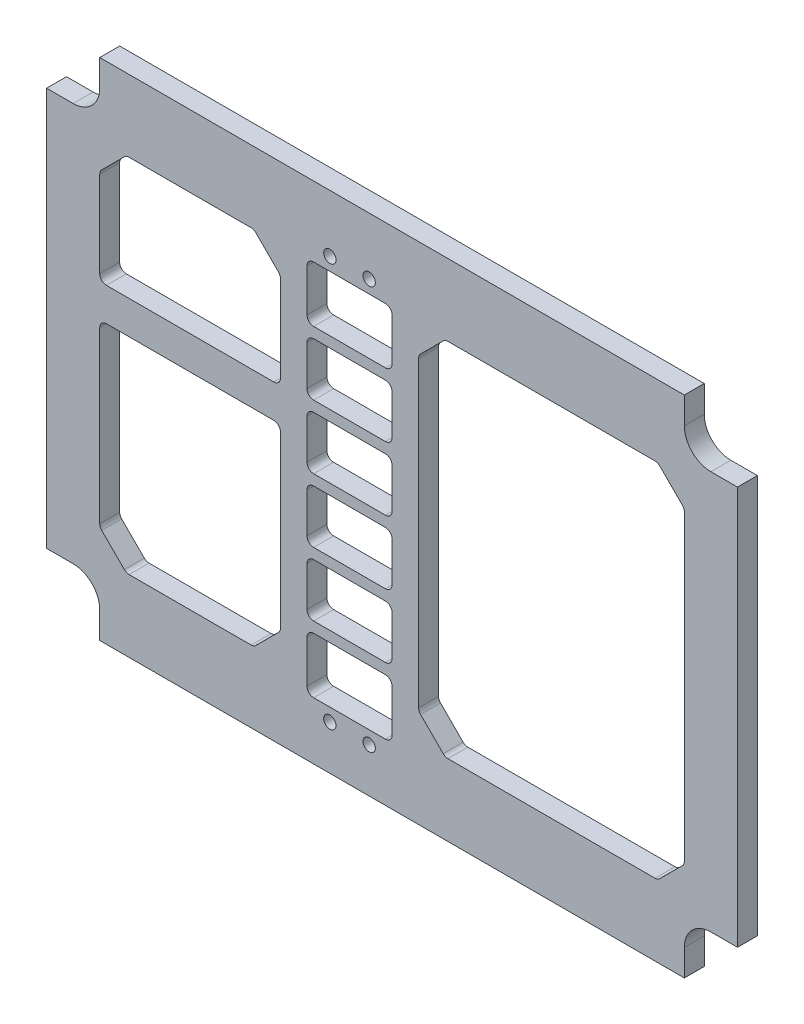
SolidWorks part; units mm, degrees
ref_plane "Front Plane" through (0, 0, 0) normal (0, 0, 1) x (1, 0, 0)
ref_plane "Top Plane" through (0, 0, 0) normal (0, 1, 0) x (1, 0, 0)
ref_plane "Right Plane" through (0, 0, 0) normal (1, 0, 0) x (0, 0, -1)
sketch "Sketch1" plane through (0, 0, 0) normal (0, 0, 1) x (1, 0, 0)
  line L0 (0, -12.7) -> (-6.35, -12.7) construction
  line L1 (-12.7, -6.35) -> (-12.7, 0) construction
  line L2 (-12.7, 0) -> (-152.4, 0) construction
  line L3 (-152.4, 0) -> (-152.4, -6.35) construction
  line L4 (-158.75, -12.7) -> (-165.1, -12.7) construction
  line L5 (-165.1, -12.7) -> (-165.1, -107.95) construction
  line L6 (-165.1, -107.95) -> (-158.75, -107.95) construction
  line L7 (-152.4, -114.3) -> (-152.4, -120.65) construction
  line L8 (-152.4, -120.65) -> (-12.7, -120.65) construction
  line L9 (-12.7, -120.65) -> (-12.7, -114.3) construction
  line L10 (-6.35, -107.95) -> (0, -107.95) construction
  line L11 (0, -107.95) -> (0, -12.7) construction
  line L12 (-102.87, -112.014) -> (-82.55, -112.014) construction
  line L13 (-82.55, -112.014) -> (-82.55, -11.684) construction
  line L14 (-82.55, -11.684) -> (-102.87, -11.684) construction
  line L15 (-102.87, -11.684) -> (-102.87, -112.014) construction
  line L16 (-19.05, -17.145) -> (-69.85, -17.145) construction
  line L17 (-69.85, -17.145) -> (-76.2, -23.495) construction
  line L18 (-76.2, -23.495) -> (-76.2, -97.155) construction
  line L19 (-76.2, -97.155) -> (-69.85, -103.505) construction
  line L20 (-69.85, -103.505) -> (-19.05, -103.505) construction
  line L21 (-19.05, -103.505) -> (-12.7, -97.155) construction
  line L22 (-12.7, -97.155) -> (-12.7, -23.495) construction
  line L23 (-12.7, -23.495) -> (-19.05, -17.145) construction
  line L24 (-152.4, -23.495) -> (-152.4, -46.355) construction
  line L25 (-152.4, -46.355) -> (-109.22, -46.355) construction
  line L26 (-109.22, -46.355) -> (-109.22, -23.495) construction
  line L27 (-109.22, -23.495) -> (-115.57, -17.145) construction
  line L28 (-115.57, -17.145) -> (-146.05, -17.145) construction
  line L29 (-146.05, -17.145) -> (-152.4, -23.495) construction
  line L30 (-109.22, -97.155) -> (-109.22, -54.2925) construction
  line L31 (-109.22, -54.2925) -> (-152.4, -54.2925) construction
  line L32 (-152.4, -54.2925) -> (-152.4, -97.155) construction
  line L33 (-152.4, -97.155) -> (-146.05, -103.505) construction
  line L34 (-146.05, -103.505) -> (-115.57, -103.505) construction
  line L35 (-115.57, -103.505) -> (-109.22, -97.155) construction
  line L36 (0, -12.7) -> (-6.35, -12.7)
  line L37 (-12.7, -6.35) -> (-12.7, 0)
  line L38 (-12.7, 0) -> (-152.4, 0)
  line L39 (-152.4, 0) -> (-152.4, -6.35)
  line L40 (-158.75, -12.7) -> (-165.1, -12.7)
  line L41 (-165.1, -12.7) -> (-165.1, -107.95)
  line L42 (-165.1, -107.95) -> (-158.75, -107.95)
  line L43 (-152.4, -114.3) -> (-152.4, -120.65)
  line L44 (-152.4, -120.65) -> (-12.7, -120.65)
  line L45 (-12.7, -120.65) -> (-12.7, -114.3)
  line L46 (-6.35, -107.95) -> (0, -107.95)
  line L47 (0, -107.95) -> (0, -12.7)
  line L48 (-102.87, -112.014) -> (-82.55, -112.014)
  line L49 (-82.55, -112.014) -> (-82.55, -11.684)
  line L50 (-82.55, -11.684) -> (-102.87, -11.684)
  line L51 (-102.87, -11.684) -> (-102.87, -112.014)
  line L52 (-19.05, -17.145) -> (-69.85, -17.145)
  line L53 (-69.85, -17.145) -> (-76.2, -23.495)
  line L54 (-76.2, -23.495) -> (-76.2, -97.155)
  line L55 (-76.2, -97.155) -> (-69.85, -103.505)
  line L56 (-69.85, -103.505) -> (-19.05, -103.505)
  line L57 (-19.05, -103.505) -> (-12.7, -97.155)
  line L58 (-12.7, -97.155) -> (-12.7, -23.495)
  line L59 (-12.7, -23.495) -> (-19.05, -17.145)
  line L60 (-152.4, -23.495) -> (-152.4, -46.355)
  line L61 (-152.4, -46.355) -> (-109.22, -46.355)
  line L62 (-109.22, -46.355) -> (-109.22, -23.495)
  line L63 (-109.22, -23.495) -> (-115.57, -17.145)
  line L64 (-115.57, -17.145) -> (-146.05, -17.145)
  line L65 (-146.05, -17.145) -> (-152.4, -23.495)
  line L66 (-109.22, -97.155) -> (-109.22, -54.2925)
  line L67 (-109.22, -54.2925) -> (-152.4, -54.2925)
  line L68 (-152.4, -54.2925) -> (-152.4, -97.155)
  line L69 (-152.4, -97.155) -> (-146.05, -103.505)
  line L70 (-146.05, -103.505) -> (-115.57, -103.505)
  line L71 (-115.57, -103.505) -> (-109.22, -97.155)
  arc A0 (-12.7, -6.35) -> (-6.35, -12.7) centre (-6.35, -6.35) ccw construction
  arc A1 (-158.75, -12.7) -> (-152.4, -6.35) centre (-158.75, -6.35) ccw construction
  arc A2 (-152.4, -114.3) -> (-158.75, -107.95) centre (-158.75, -114.3) ccw construction
  arc A3 (-6.35, -107.95) -> (-12.7, -114.3) centre (-6.35, -114.3) ccw construction
  arc A4 (-12.7, -6.35) -> (-6.35, -12.7) centre (-6.35, -6.35) ccw
  arc A5 (-158.75, -12.7) -> (-152.4, -6.35) centre (-158.75, -6.35) ccw
  arc A6 (-152.4, -114.3) -> (-158.75, -107.95) centre (-158.75, -114.3) ccw
  arc A7 (-6.35, -107.95) -> (-12.7, -114.3) centre (-6.35, -114.3) ccw
extrude "Boss-Extrude1" add sketch "Sketch1" along normal blind 4.7625
sketch "Sketch2" plane through (0, 0, 0) normal (0, 0, -1) x (-1, 0, 0)
  line L9 (105.87, -115.014) -> (105.87, -8.684)
  line L10 (79.55, -115.014) -> (105.87, -115.014)
  line L11 (79.55, -8.684) -> (79.55, -115.014)
  line L12 (105.87, -8.684) -> (79.55, -8.684)
  line L13 (105.87, -115.014) -> (105.87, -8.684)
  line L14 (79.55, -115.014) -> (105.87, -115.014)
  line L15 (79.55, -8.684) -> (79.55, -115.014)
  line L16 (105.87, -8.684) -> (79.55, -8.684)
  dimension "D1" = 3
extrude "Cut-Extrude1" cut sketch "Sketch2" against normal through all
fillet "Fillet1" radius 1.5875 24 edges at (-109.22, -54.2925, 2.3813) (-152.4, -54.2925, 2.3813) (-146.05, -103.505, 2.3813) (-115.57, -103.505, 2.3813) (-109.22, -97.155, 2.3813) (-152.4, -46.355, 2.3813) (-109.22, -46.355, 2.3813) (-109.22, -23.495, 2.3813) (-115.57, -17.145, 2.3813) (-146.05, -17.145, 2.3813) (-152.4, -23.495, 2.3813) (-69.85, -17.145, 2.3813) (-76.2, -23.495, 2.3813) (-76.2, -97.155, 2.3813) (-69.85, -103.505, 2.3813) (-19.05, -103.505, 2.3813) (-12.7, -97.155, 2.3813) (-12.7, -23.495, 2.3813) (-19.05, -17.145, 2.3813) (-79.55, -115.014, 2.3813) (-79.55, -8.684, 2.3813) (-105.87, -8.684, 2.3813) (-105.87, -115.014, 2.3813) (-152.4, -97.155, 2.3813)
sketch "Sketch4" plane through (0, 0, 4.7625) normal (0, 0, 1) x (1, 0, 0)
  line L0 (-79.55, -10.2715) -> (-79.55, -113.4265) construction
  line L1 (-81.1375, -115.014) -> (-104.2825, -115.014) construction
  line L2 (-105.87, -113.4265) -> (-105.87, -10.2715) construction
  line L3 (-104.2825, -8.684) -> (-81.1375, -8.684) construction
  line L4 (-79.55, -10.2715) -> (-79.55, -113.4265)
  line L5 (-81.1375, -115.014) -> (-104.2825, -115.014)
  line L6 (-105.87, -113.4265) -> (-105.87, -10.2715)
  line L7 (-104.2825, -8.684) -> (-81.1375, -8.684)
  line L8 (-82.55, -18.3515) -> (-82.55, -28.5115) construction
  line L9 (-84.1375, -30.099) -> (-101.2825, -30.099) construction
  line L10 (-102.87, -28.5115) -> (-102.87, -18.3515) construction
  line L12 (-82.55, -34.2265) -> (-82.55, -43.7515) construction
  line L13 (-84.1375, -45.339) -> (-101.2825, -45.339) construction
  line L14 (-102.87, -43.7515) -> (-102.87, -34.2265) construction
  line L15 (-101.2825, -32.639) -> (-84.1375, -32.639) construction
  line L16 (-82.55, -49.4665) -> (-82.55, -58.9915) construction
  line L17 (-84.1375, -60.579) -> (-101.2825, -60.579) construction
  line L18 (-102.87, -58.9915) -> (-102.87, -49.4665) construction
  line L19 (-101.2825, -47.879) -> (-84.1375, -47.879) construction
  line L20 (-82.55, -64.7065) -> (-82.55, -74.2315) construction
  line L21 (-84.1375, -75.819) -> (-101.2825, -75.819) construction
  line L22 (-102.87, -74.2315) -> (-102.87, -64.7065) construction
  line L23 (-101.2825, -63.119) -> (-84.1375, -63.119) construction
  line L24 (-82.55, -79.9465) -> (-82.55, -89.4715) construction
  line L25 (-84.1375, -91.059) -> (-101.2825, -91.059) construction
  line L26 (-102.87, -89.4715) -> (-102.87, -79.9465) construction
  line L27 (-101.2825, -78.359) -> (-84.1375, -78.359) construction
  line L28 (-82.55, -95.1865) -> (-82.55, -105.3465) construction
  line L30 (-102.87, -105.3465) -> (-102.87, -95.1865) construction
  line L31 (-101.2825, -93.599) -> (-84.1375, -93.599) construction
  line L32 (-82.55, -18.3515) -> (-82.55, -28.5115)
  line L33 (-84.1375, -30.099) -> (-101.2825, -30.099)
  line L34 (-102.87, -28.5115) -> (-102.87, -18.3515)
  line L35 (-101.2825, -16.764) -> (-84.1375, -16.764)
  line L36 (-82.55, -34.2265) -> (-82.55, -43.7515)
  line L37 (-84.1375, -45.339) -> (-101.2825, -45.339)
  line L38 (-102.87, -43.7515) -> (-102.87, -34.2265)
  line L39 (-101.2825, -32.639) -> (-84.1375, -32.639)
  line L40 (-82.55, -49.4665) -> (-82.55, -58.9915)
  line L41 (-84.1375, -60.579) -> (-101.2825, -60.579)
  line L42 (-102.87, -58.9915) -> (-102.87, -49.4665)
  line L43 (-101.2825, -47.879) -> (-84.1375, -47.879)
  line L44 (-82.55, -64.7065) -> (-82.55, -74.2315)
  line L45 (-84.1375, -75.819) -> (-101.2825, -75.819)
  line L46 (-102.87, -74.2315) -> (-102.87, -64.7065)
  line L47 (-101.2825, -63.119) -> (-84.1375, -63.119)
  line L48 (-82.55, -79.9465) -> (-82.55, -89.4715)
  line L49 (-84.1375, -91.059) -> (-101.2825, -91.059)
  line L50 (-102.87, -89.4715) -> (-102.87, -79.9465)
  line L51 (-101.2825, -78.359) -> (-84.1375, -78.359)
  line L52 (-82.55, -95.1865) -> (-82.55, -105.3465)
  line L53 (-84.1375, -106.934) -> (-101.2825, -106.934)
  line L54 (-102.87, -105.3465) -> (-102.87, -95.1865)
  line L55 (-101.2825, -93.599) -> (-84.1375, -93.599)
  arc A0 (-79.55, -10.2715) -> (-81.1375, -8.684) centre (-81.1375, -10.2715) ccw construction
  arc A1 (-81.1375, -115.014) -> (-79.55, -113.4265) centre (-81.1375, -113.4265) ccw construction
  arc A2 (-105.87, -113.4265) -> (-104.2825, -115.014) centre (-104.2825, -113.4265) ccw construction
  arc A3 (-104.2825, -8.684) -> (-105.87, -10.2715) centre (-104.2825, -10.2715) ccw construction
  arc A4 (-79.55, -10.2715) -> (-81.1375, -8.684) centre (-81.1375, -10.2715) ccw
  arc A5 (-81.1375, -115.014) -> (-79.55, -113.4265) centre (-81.1375, -113.4265) ccw
  arc A6 (-105.87, -113.4265) -> (-104.2825, -115.014) centre (-104.2825, -113.4265) ccw
  arc A7 (-104.2825, -8.684) -> (-105.87, -10.2715) centre (-104.2825, -10.2715) ccw
  arc A11 (-84.1375, -30.099) -> (-82.55, -28.5115) centre (-84.1375, -28.5115) ccw construction
  arc A12 (-102.87, -28.5115) -> (-101.2825, -30.099) centre (-101.2825, -28.5115) ccw construction
  arc A13 (-101.2825, -16.764) -> (-102.87, -18.3515) centre (-101.2825, -18.3515) ccw construction
  arc A14 (-82.55, -34.2265) -> (-84.1375, -32.639) centre (-84.1375, -34.2265) ccw construction
  arc A15 (-84.1375, -45.339) -> (-82.55, -43.7515) centre (-84.1375, -43.7515) ccw construction
  arc A16 (-102.87, -43.7515) -> (-101.2825, -45.339) centre (-101.2825, -43.7515) ccw construction
  arc A17 (-101.2825, -32.639) -> (-102.87, -34.2265) centre (-101.2825, -34.2265) ccw construction
  arc A18 (-82.55, -49.4665) -> (-84.1375, -47.879) centre (-84.1375, -49.4665) ccw construction
  arc A19 (-84.1375, -60.579) -> (-82.55, -58.9915) centre (-84.1375, -58.9915) ccw construction
  arc A20 (-102.87, -58.9915) -> (-101.2825, -60.579) centre (-101.2825, -58.9915) ccw construction
  arc A21 (-101.2825, -47.879) -> (-102.87, -49.4665) centre (-101.2825, -49.4665) ccw construction
  arc A22 (-82.55, -64.7065) -> (-84.1375, -63.119) centre (-84.1375, -64.7065) ccw construction
  arc A23 (-84.1375, -75.819) -> (-82.55, -74.2315) centre (-84.1375, -74.2315) ccw construction
  arc A24 (-102.87, -74.2315) -> (-101.2825, -75.819) centre (-101.2825, -74.2315) ccw construction
  arc A25 (-101.2825, -63.119) -> (-102.87, -64.7065) centre (-101.2825, -64.7065) ccw construction
  arc A26 (-82.55, -79.9465) -> (-84.1375, -78.359) centre (-84.1375, -79.9465) ccw construction
  arc A27 (-84.1375, -91.059) -> (-82.55, -89.4715) centre (-84.1375, -89.4715) ccw construction
  arc A28 (-102.87, -89.4715) -> (-101.2825, -91.059) centre (-101.2825, -89.4715) ccw construction
  arc A29 (-101.2825, -78.359) -> (-102.87, -79.9465) centre (-101.2825, -79.9465) ccw construction
  arc A30 (-82.55, -95.1865) -> (-84.1375, -93.599) centre (-84.1375, -95.1865) ccw construction
  arc A31 (-84.1375, -106.934) -> (-82.55, -105.3465) centre (-84.1375, -105.3465) ccw construction
  arc A33 (-101.2825, -93.599) -> (-102.87, -95.1865) centre (-101.2825, -95.1865) ccw construction
  circle A36 centre (-88.011, -13.6525) radius 1.4732
  circle A37 centre (-97.409, -13.6525) radius 1.4732
  arc A38 (-82.55, -18.3515) -> (-84.1375, -16.764) centre (-84.1375, -18.3515) ccw
  arc A39 (-84.1375, -30.099) -> (-82.55, -28.5115) centre (-84.1375, -28.5115) ccw
  arc A40 (-102.87, -28.5115) -> (-101.2825, -30.099) centre (-101.2825, -28.5115) ccw
  arc A41 (-101.2825, -16.764) -> (-102.87, -18.3515) centre (-101.2825, -18.3515) ccw
  arc A42 (-82.55, -34.2265) -> (-84.1375, -32.639) centre (-84.1375, -34.2265) ccw
  arc A43 (-84.1375, -45.339) -> (-82.55, -43.7515) centre (-84.1375, -43.7515) ccw
  arc A44 (-102.87, -43.7515) -> (-101.2825, -45.339) centre (-101.2825, -43.7515) ccw
  arc A45 (-101.2825, -32.639) -> (-102.87, -34.2265) centre (-101.2825, -34.2265) ccw
  arc A46 (-82.55, -49.4665) -> (-84.1375, -47.879) centre (-84.1375, -49.4665) ccw
  arc A47 (-84.1375, -60.579) -> (-82.55, -58.9915) centre (-84.1375, -58.9915) ccw
  arc A48 (-102.87, -58.9915) -> (-101.2825, -60.579) centre (-101.2825, -58.9915) ccw
  arc A49 (-101.2825, -47.879) -> (-102.87, -49.4665) centre (-101.2825, -49.4665) ccw
  arc A50 (-82.55, -64.7065) -> (-84.1375, -63.119) centre (-84.1375, -64.7065) ccw
  arc A51 (-84.1375, -75.819) -> (-82.55, -74.2315) centre (-84.1375, -74.2315) ccw
  arc A52 (-102.87, -74.2315) -> (-101.2825, -75.819) centre (-101.2825, -74.2315) ccw
  arc A53 (-101.2825, -63.119) -> (-102.87, -64.7065) centre (-101.2825, -64.7065) ccw
  arc A54 (-82.55, -79.9465) -> (-84.1375, -78.359) centre (-84.1375, -79.9465) ccw
  arc A55 (-84.1375, -91.059) -> (-82.55, -89.4715) centre (-84.1375, -89.4715) ccw
  arc A56 (-102.87, -89.4715) -> (-101.2825, -91.059) centre (-101.2825, -89.4715) ccw
  arc A57 (-101.2825, -78.359) -> (-102.87, -79.9465) centre (-101.2825, -79.9465) ccw
  arc A58 (-82.55, -95.1865) -> (-84.1375, -93.599) centre (-84.1375, -95.1865) ccw
  arc A59 (-84.1375, -106.934) -> (-82.55, -105.3465) centre (-84.1375, -105.3465) ccw
  arc A60 (-102.87, -105.3465) -> (-101.2825, -106.934) centre (-101.2825, -105.3465) ccw
  arc A61 (-101.2825, -93.599) -> (-102.87, -95.1865) centre (-101.2825, -95.1865) ccw
  circle A62 centre (-97.409, -110.0455) radius 1.4732
  circle A63 centre (-88.011, -110.0455) radius 1.4732
extrude "Boss-Extrude2" add sketch "Sketch4" against normal through all
